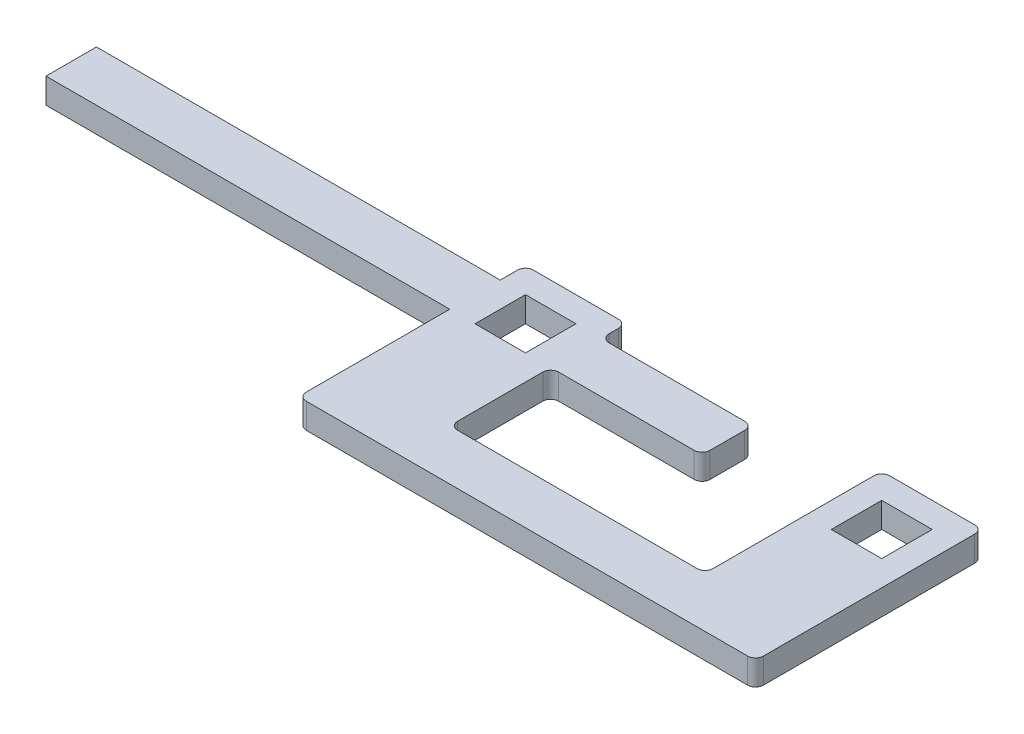
SolidWorks part; units mm, degrees
material "Beech"
ref_plane "Front Plane" through (0, 0, 0) normal (0, 0, 1) x (1, 0, 0)
ref_plane "Top Plane" through (0, 0, 0) normal (0, 1, 0) x (1, 0, 0)
ref_plane "Right Plane" through (0, 0, 0) normal (1, 0, 0) x (0, 0, -1)
sketch "Sketch1" plane through (0, 0, 0) normal (0, 1, 0) x (1, 0, 0)
  line L0 (0, 0) -> (0, 19.05)
  line L1 (0, 0) -> (19.05, 0)
  line L2 (0, 28.575) -> (12.7, 28.575)
  line L3 (12.7, 6.35) -> (12.7, 19.05)
  line L4 (44.825, 28.575) -> (44.825, 6.35)
  line L5 (44.825, 28.575) -> (57.525, 28.575)
  line L6 (42.65, 0) -> (57.525, 0)
  line L7 (57.525, 28.575) -> (57.525, 0)
  line L8 (12.7, 6.35) -> (44.825, 6.35)
  line L10 (12.7, 19.05) -> (31.75, 19.05)
  line L11 (19.05, 0) -> (42.65, 0)
  line L12 (3.175, 25.4) -> (3.175, 19.05)
  line L13 (3.175, 25.4) -> (9.525, 25.4)
  line L14 (3.175, 19.05) -> (9.525, 19.05)
  line L15 (9.525, 25.4) -> (9.525, 19.05)
  line L16 (48, 25.4) -> (48, 19.05)
  line L17 (48, 25.4) -> (54.35, 25.4)
  line L18 (48, 19.05) -> (54.35, 19.05)
  line L19 (54.35, 25.4) -> (54.35, 19.05)
  line L20 (0, 25.4) -> (-50.8, 25.4)
  line L21 (12.7, 25.4) -> (31.75, 25.4)
  line L22 (-50.8, 25.4) -> (-50.8, 19.05)
  line L23 (0, 19.05) -> (-50.8, 19.05)
  line L24 (0, 25.4) -> (0, 28.575)
  line L25 (31.75, 19.05) -> (31.75, 25.4)
  line L26 (12.7, 25.4) -> (12.7, 28.575)
  dimension "D1" = 6.35
  dimension "D2" = 6.35
  dimension "D3" = 6.35
  dimension "D4" = 6.35
  dimension "D5" = 44.825
  dimension "D6" = 3.175
  dimension "D7" = 19.05
  dimension "D8" = 3.175
  dimension "D9" = 3.175
  dimension "D10" = 3.175
  dimension "D11" = 3.175
  dimension "D12" = 3.175
  dimension "D13" = 19.05
  dimension "D14" = 50.8
  dimension "D15" = 6.35
  dimension "D16" = 6.35
  dimension "D17" = 19.05
extrude "Elastic_Extrude" add sketch "Sketch1" along normal blind 3.175
fillet "Elastic_CornerFillet" radius 1 12 edges at (12.7, 1.5875, -6.35) (44.825, 1.5875, -6.35) (44.825, 1.5875, -28.575) (57.525, 1.5875, -28.575) (57.525, 1.5875, 0) (0, 1.5875, 0) (0, 1.5875, -28.575) (12.7, 1.5875, -19.05) (31.75, 1.5875, -19.05) (31.75, 1.5875, -25.4) (12.7, 1.5875, -25.4) (12.7, 1.5875, -28.575)
equation "\"CageLeftBottomEdge\"=22.11mm"
equation "\"CageLeftTopEdge\"=22.11mm"
equation "\"CageRightBottomEdge\"=21.63mm"
equation "\"CageRightTopEdge\"=21.63mm"
equation "\"CageHeight\"=86.04mm"
equation "\"CageLength\"=73.76mm"
equation "\"CageTopScrewClearance\"=10mm"
equation "\"CageBottomScrewClearance\"=25mm"
equation "\"CageLeftTopDepth\"= 11.65mm"
equation "\"CageLeftBottomDepth\"=11.11mm"
equation "\"CageLeftTopHeight\"=8.56175mm"
equation "\"CageLeftBottomHeight\"=16mm"
equation "\"CageRightTopDepth\"= 11.05mm"
equation "\"CageRightBottomDepth\"=10.58mm"
equation "\"CageRightTopHeight\"=9.6mm"
equation "\"CageRightBottomHeight\"=15.49mm"
equation "\"CageLeftTopChannelDepth\"=2.41908mm"
equation "\"CageLeftBottomChannelDepth\"=2.588mm"
equation "\"CageLeftChannelHeight\"=11.7mm"
equation "\"CageRightTopChannelDepth\"=2.32mm"
equation "\"CageRightBottomChannelDepth\"=2.318mm"
equation "\"CageRightChannelHeight\"=10mm"
equation "\"CageChanRelHeight\"=23.99mm"
equation "\"CageChanRelDepth\"=5.492mm"
equation "\"CageChamberRadius\"=16.261mm"
equation "\"CageScrewDiameter\"=4.8mm"
equation "\"CageSetScrewDiameter\"=3.5mm"
equation "\"CageAxleRadius\"=6.639mm"
equation "\"CageAxleKeyHeight\"=1.619mm"
equation "\"CageAxleKeyWidth\"=2.662mm"
equation "\"CageHoseWindowWidth\"=16.29mm"
equation "\"CageHoseWindowHeight\"=26.5mm"
equation "\"CageHoseWindow-Edge\"=8.89mm"
equation "\"CageScrew-VerticalEdge\"=5.0mm"
equation "\"CageScrew-HorizontalEdge\"=7.5mm"
equation "\"CageScrew-HoseCornerScrewEdge\"=4.45mm"
equation "\"CageAxle-BottomEdge\"=56.05mm"
equation "\"CageAxle-FrontEdge\"=46.03mm"
equation "\"CageBackSetScrew-Axle\"=40mm"
equation "\"CageFrontSetScrew-Axle\"=22mm"
equation "\"CageVelocityWindow-BackEdge\"=34.8mm"
equation "\"CageVelocityWindow-BottomEdge\"=27.55mm"
equation "\"CageVelocityWindowHeight\"=22.29mm"
equation "\"CageVelocityWindowWidth\"=12.61mm"
equation "\"TriggerSlot-BottomEdge\"=6.35mm"
equation "\"TriggerSlot-FrontEdge\"=15mm"
equation "\"TriggerSlotSize\"=6.7mm"
equation "\"TriggerRackOffset\"=.236224in"
equation "\"TriggerSlotSizeInt\"=.25in"
equation "\"MotorMountLegLength\"=.25in"
equation "\"GearOffset\"=.264907in"
equation "\"TriggerSlotSpacing\"=.25in"
equation "\"TriggerMiniSlotWidth\"=3.5mm"
equation "\"TriggerRackWidth\"=6.5mm"
equation "\"whitemotordepth\"=11.27mm"
equation "\"whitemotorbackdepth\"=3.845mm"
equation "\"whitemotoraxledepth\" = 3.5mm"
equation "\"whitemotoraxleoffset\"=11.4mm"
equation "\"whitemotorwidth\"=12.07mm"
equation "\"whitemotorheight\"=16.68mm"
equation "\"whitemotorcylinderlength\" =13.04mm"
equation "\"whitemotorcylinderradius\"=3.845mm"
equation "\"whitemotorcylinderoffset\"=2.35mm"
equation "\"whitemotorcutoutlength\"=1.88mm"
equation "\"whitemotorouterrad\"=5mm"
equation "\"D4@Sketch1\"=\"elasticrackpegsize\""
equation "\"elasticrackpegspacing\"=1.76476378in"
equation "\"D5@Sketch1\"=\"elasticrackpegspacing\""
equation "\"D6@Sketch1\"=\"elasticrackpegbuffer\""
equation "\"elasticrackpegsize\"=.25in"
equation "\"D1@Sketch1\"=\"elasticrackpegsize\""
equation "\"D2@Sketch1\"=\"elasticrackpegsize\""
equation "\"D3@Sketch1\"=\"elasticrackpegsize\""
equation "\"elasticracklength\"=2in"
equation "\"D14@Sketch1\"=\"elasticracklength\""
equation "\"elasticrackpegbuffer\"=.125in"
equation "\"D11@Sketch1\"=\"elasticrackpegbuffer\""
equation "\"D12@Sketch1\"=\"elasticrackpegbuffer\""
equation "\"D10@Sketch1\"=\"elasticrackpegbuffer\""
equation "\"D9@Sketch1\"=\"elasticrackpegbuffer\""
equation "\"D8@Sketch1\"=\"elasticrackpegbuffer\""
equation "\"elasticbaybuffer\"=.25in"
equation "\"D15@Sketch1\"=\"elasticbaybuffer\""
equation "\"D16@Sketch1\"=\"elasticbaybuffer\""
equation "\"whitemotorinnerrad\"=2.95mm"
equation "\"elasticbaydepth\"=.75in"
equation "\"D7@Sketch1\"=\"elasticbaydepth\""
equation "\"D13@Sketch1\"=\"elasticbaydepth\""
equation "\"D17@Sketch1\"=\"elasticbaydepth\""
equation "\"elasticdepth\"=.125in"
equation "\"D1@Elastic_Extrude\"=\"elasticdepth\""
equation "\"motormountwidth\"=12mm"
equation "\"motormountcornerfillet\"=3mm"
equation "\"pandiscradius\"=14in"
equation "\"towermaterialwidth\"=.25in"
equation "\"towerslotlength\"=.5in"
equation "\"towermarkerspace\"=5in"
equation "\"towerslothorizoffset\"=1in"
equation "\"towerslothorizspacing\"=2in"
equation "\"towerslotvertoffset\"=3in"
equation "\"towerslotvertspacing\"=1in"
equation "\"towerheight\"=12in"
equation "\"towerupslot\"=1in"
equation "\"toweraxle\"=.5in"
equation "\"stepperouterrad\"=10mm"
equation "\"stepperscrewsize\"=3.45mm"
equation "\"stepperscrewc2c\"=49.5mm"
equation "\"stepperdepthoffset\"=24mm"
equation "\"stepperhorizoffset\"=22.91mm"
equation "\"shaftslotOD\"=18.8mm"
equation "\"shaftslotID\"=13.28mm"
equation "\"shaftkeywidth\"=2.67mm"
equation "\"shaftkeydepth\"=1.8mm"
equation "\"shaftcollartotaldepth\"=12.5mm"
equation "\"shaftsquaredepth\"=6mm"
equation "\"shaftsetscrewsize\"=3.5mm"
equation "\"shaftkeytightdepth\"=1.85mm"
equation "\"shaftslottightID\"=12.78mm"
equation "\"shaftsetscrewoffset\"=9mm"
equation "\"cagecollartotaldepth\"=10mm"
equation "\"cagecollartotalwidth\"=35mm"
equation "\"cagecollarbasedepth\"=4mm"
equation "\"gearhubintdiam\"=30mm"
equation "\"gearhubintwid\"=15mm"
equation "\"towerspeedwidth\"=2in"
equation "\"towerspeedheight\"=8in"
equation "\"towerspeedgap\"=2in"
equation "\"stepperaxleflat\"=.037in"
equation "\"stepperaxlerad\"=0.11811024in"
equation "\"ajaxaxlesize\"=3.87mm"
equation "\"ajaxinnercut\"=2.3mm"
equation "\"ajaxwidth\"=6.1mm"
equation "\"ajaxdiametral\"=25.8854"
equation "\"ajaxcutoutdepth\"=2.3mm"
equation "\"ajax4020gap\"=29.5mm"
equation "\"ajax4010gap\"=24.5mm"
equation "\"ajax20hubbuffer\"=6.1mm"
equation "\"ajax20hubholeoffset\"=.19685in"
equation "\"ajax20hubholesize\"=.059055in"
equation "\"ajax20cutoutint\"=13.4mm"
equation "\"ajax40hubholesize\"=7.21mm"
equation "\"ajax40hubholeoffset\"=10mm"
equation "\"ajax40hubbuffer\"=8.9mm"
equation "\"ajax40cutoutint\"=32.6mm"
equation "\"bearingpandiscrad\"=6.8in"
equation "\"bearingpandiscang\"=48.75deg"
equation "\"bearingclearholedist\"=4.7345in"
equation "\"bearingclearholesize\"=.5in"
equation "\"bearingclearholeang\"=22.5deg"
equation "\"bearingmountholedist\"=4.25in"
equation "\"bearingwirehole\"=1.5in"
equation "\"no6diam\"=.146in"
equation "\"shortconangle\"=20deg"
equation "\"shortconlen\"=.875in"
equation "\"longconlen\"=1.25in"
equation "\"longconangle\"=15deg"
